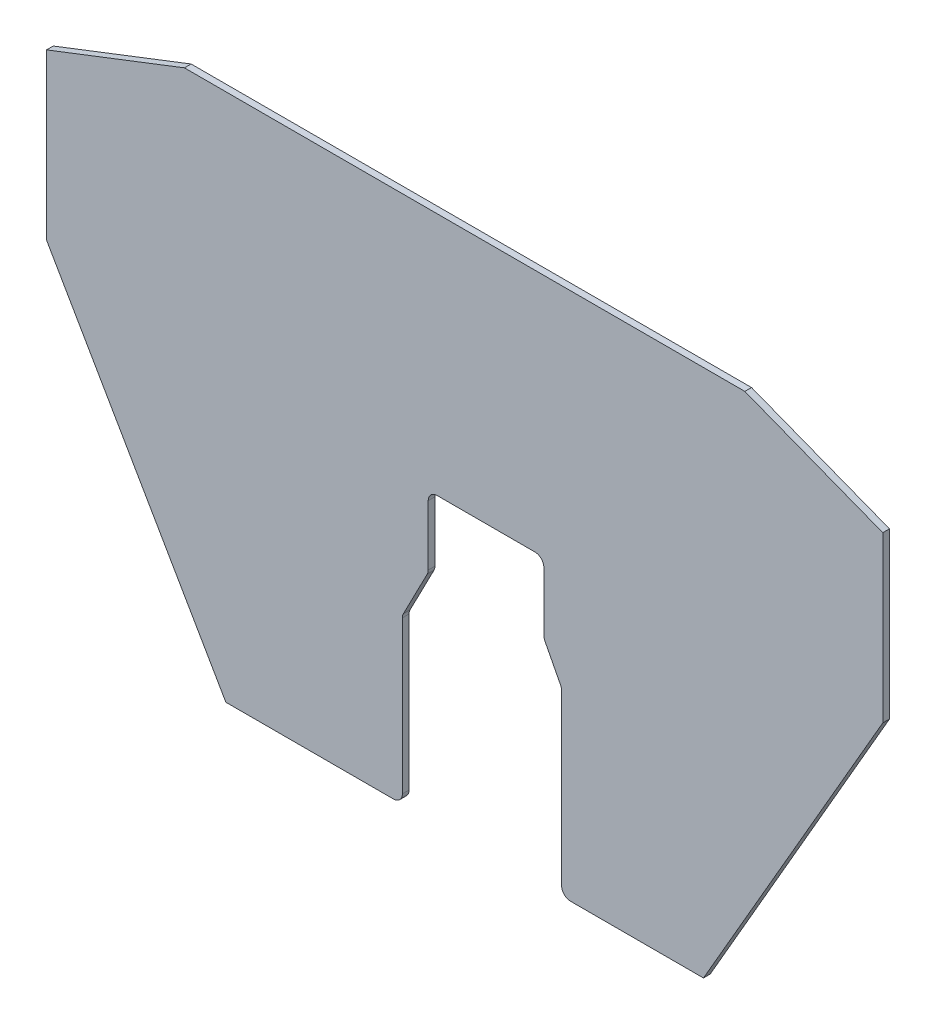
SolidWorks part; units mm, degrees
ref_plane "Front Plane" through (0, 0, 0) normal (0, 0, 1) x (1, 0, 0)
ref_plane "Top Plane" through (0, 0, 0) normal (0, 1, 0) x (1, 0, 0)
ref_plane "Right Plane" through (0, 0, 0) normal (1, 0, 0) x (0, 0, -1)
sketch "Sketch1" plane through (0, 0, 0) normal (0, 0, 1) x (1, 0, 0)
  line L0 (0, 205.7814) -> (0, -171.6157) construction
  line L1 (170.4677, -171.6157) -> (69.2396, -171.6157)
  line L2 (298.45, 50.0562) -> (298.45, 167.6814)
  line L3 (200.025, 205.7814) -> (63.5, 205.7814)
  line L4 (-298.45, 50.0562) -> (-298.45, 167.6814)
  line L5 (282.9448, -195.0905) -> (-298.45, 205.7814) construction
  line L6 (298.45, 205.7814) -> (-296.0019, -204.0934) construction
  line L7 (177.8, -158.9157) -> (-177.8, -158.9157) construction
  line L8 (-170.4677, -171.6157) -> (-298.45, 50.0562)
  line L9 (170.4677, -171.6157) -> (298.45, 50.0562)
  line L10 (-63.5, 205.7814) -> (-200.025, 205.7814)
  line L11 (-63.5, 205.7814) -> (63.5, 205.7814)
  line L12 (-63.5, -171.6157) -> (-170.4677, -171.6157)
  line L13 (-44.45, -54.8862) -> (-44.45, -171.6157)
  line L14 (50.8, 31.5843) -> (56.5396, 31.5843)
  line L15 (-298.45, 167.6814) -> (-200.025, 205.7814)
  line L16 (-44.45, -171.6157) -> (-63.5, -171.6157)
  line L17 (63.5, -19.2157) -> (-63.5, -171.6157) construction
  line L18 (63.5, -171.6157) -> (-63.5, -19.2157) construction
  line L19 (50.8, 31.5843) -> (-26.0104, 31.5843)
  line L20 (298.45, 167.6814) -> (200.025, 205.7814)
  line L21 (56.5396, 31.5843) -> (56.5396, -18.4436)
  line L22 (-26.0104, 31.5843) -> (-26.0104, -19.2157)
  line L23 (50.8, 31.5843) -> (-50.8, -19.2157) construction
  line L24 (50.8, -19.2157) -> (-50.8, 31.5843) construction
  line L25 (-26.0104, -19.2157) -> (-44.45, -54.8862)
  line L26 (56.5396, -18.4436) -> (69.2396, -43.0112)
  line L27 (69.2396, -43.0112) -> (69.2396, -171.6157)
  point P0 (0, 0)
  point P11 (0, -158.9157)
  point P15 (0, 155.9882)
  point P17 (0, -95.4157)
  point P23 (0, 6.1843)
  point P28 (-38.1, 31.5843)
  point P29 (-63.5, -43.7833)
  point P30 (63.5, -43.7833)
  point P31 (-38.1, -19.2157)
  dimension "D1" = 596.9
  dimension "D2" = 127
  dimension "D3" = 355.6
  dimension "D4" = 12.7
  dimension "D5" = 120
  dimension "D6" = 377.3971
  dimension "D7" = 152.4
  dimension "D8" = 82.55
  dimension "D9" = 50.8
  dimension "D10" = 98.425
  dimension "D11" = 38.1
extrude "Boss-Extrude1" add sketch "Sketch1" along normal blind 4.7752
fillet "Fillet1" radius 6.35 8 edges at (-26.0104, 31.5843, 2.3876) (-26.0104, -19.2157, 2.3876) (-44.45, -54.8862, 2.3876) (-44.45, -171.6157, 2.3876) (69.2396, -171.6157, 2.3876) (69.2396, -43.0112, 2.3876) (56.5396, -18.4436, 2.3876) (56.5396, 31.5843, 2.3876)
